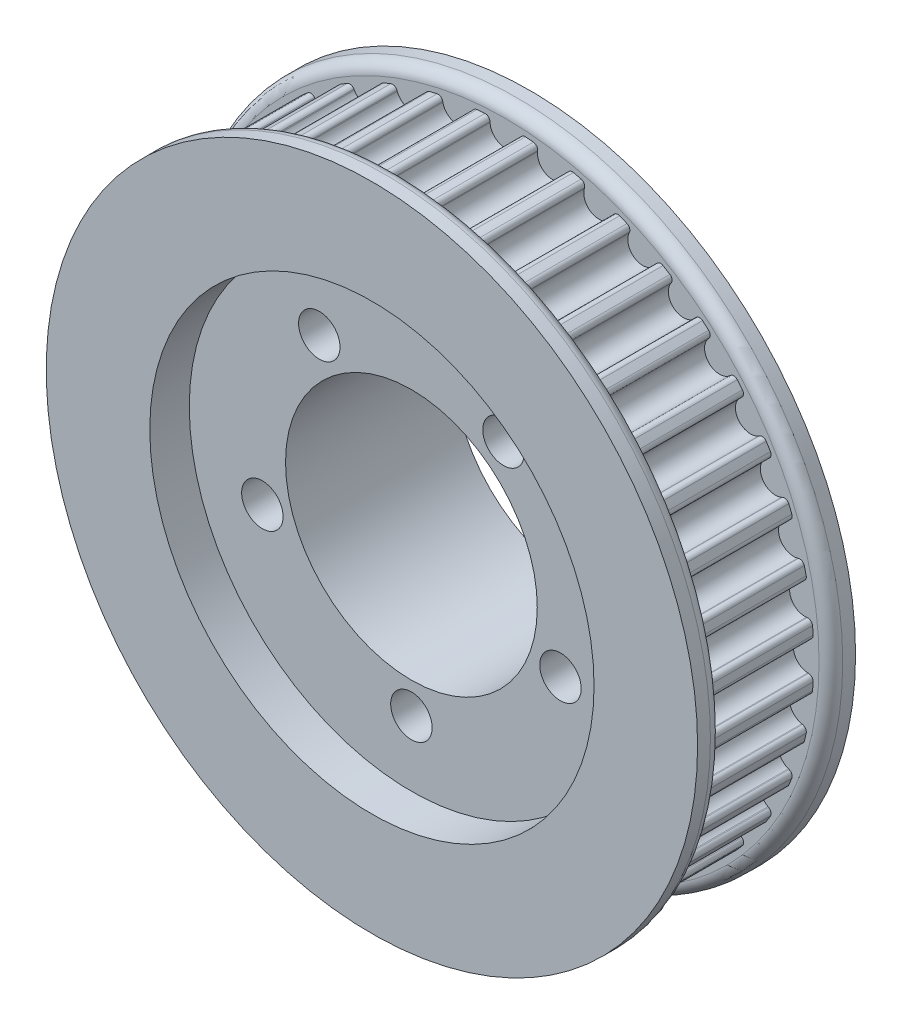
SolidWorks part; units mm, degrees
material "6061 합금"
ref_plane "정면" through (0, 0, 0) normal (0, 0, 1) x (1, 0, 0)
ref_plane "윗면" through (0, 0, 0) normal (0, 1, 0) x (1, 0, 0)
ref_plane "우측면" through (0, 0, 0) normal (1, 0, 0) x (0, 0, -1)
sketch "스케치3" plane through (0, 0, 0) normal (0, 0, 1) x (1, 0, 0)
  line L0 (0, 0) -> (0, 31.2595) construction
  line L1 (0, 0) -> (-4.9795, 31.4391) construction
  line L2 (0, 31.2595) -> (0, 32.9895) construction
  line L3 (-1.5331, 30.6478) -> (-1.5617, 31.2205)
  line L4 (1.5331, 30.6478) -> (1.5617, 31.2205)
  circle A0 centre (0, 0) radius 31.831 construction
  circle A1 centre (0, 0) radius 32.9895 construction
  circle A2 centre (0, 0) radius 31.2595
  circle A3 centre (0, 30.7245) radius 1.535
  dimension "D2" = 63.662
  dimension "D5" = 3.07
  dimension "D3" = 62.519
  dimension "D1" = 9
  dimension "D4" = 2.07
  dimension "D6" = 3.8
extrude "보스-돌출2" add sketch "스케치3" along normal mid plane 11 contours A2
extrude "컷-돌출2" cut sketch "스케치3<3>" against normal through all and the other way through all contours A3 A2 L3 | A2 A3 | A3 L4 A2 region at (0, 30.3451, 0) region at (-1.5216, 31.0799, 0) region at (1.5216, 31.0799, 0)
sketch "스케치3<3>" plane through (0, 0, 0) normal (0, 0, 1) x (1, 0, 0) same geometry as "스케치3"
fillet "필렛1" radius 0.48 2 edges at (1.5617, 31.2205, 0) (-1.5617, 31.2205, 0)
pattern_circular "원형 패턴1" count 40 over 360 about axis through (0, 0, 5.5) along (0, 0, -1) of "컷-돌출2", "필렛1"
sketch "스케치8" plane through (0, 0, 5.5) normal (0, 0, 1) x (1, 0, 0)
  circle A1 centre (0, 0) radius 32.9895 construction
  circle A2 centre (0, 0) radius 32.9895
extrude "보스-돌출3" add sketch "스케치8" along normal blind 2.5
fillet "필렛2" radius 1.2 1 edges at (32.9895, 0, 5.5)
mirror "대칭 복사1" about plane through (0, 0, 0) normal (0, 0, 1) of "보스-돌출3", "필렛2"
sketch "스케치17" plane through (0, 0, -8) normal (0, 0, -1) x (-1, 0, 0)
  circle A0 centre (0, 0) radius 20
  dimension "D1" = 40
extrude "보스-돌출4" add sketch "스케치17" along normal blind 5 contours A0
sketch "스케치10" plane through (0, 0, 0) normal (0, 0, 1) x (1, 0, 0)
  line L0 (0, 0) -> (0, 15.875) construction
  circle A0 centre (0, 15.875) radius 2.675
  circle A1 centre (9.3311, 12.8431) radius 2.675 construction
  circle A2 centre (15.098, 4.9056) radius 2.675
  circle A3 centre (15.098, -4.9056) radius 2.675 construction
  circle A4 centre (9.3311, -12.8431) radius 2.675
  circle A5 centre (0, -15.875) radius 2.675 construction
  circle A6 centre (-9.3311, -12.8431) radius 2.675
  circle A7 centre (-15.098, -4.9056) radius 2.675 construction
  circle A8 centre (-15.098, 4.9056) radius 2.675
  circle A9 centre (-9.3311, 12.8431) radius 2.675 construction
  point P25 (0, 0)
  dimension "D1" = 5.35
  dimension "D2" = 15.875
  dimension "D3" = 10
hole_wizard "M5x0.8 탭을 위한 탭 드릴2" positions "스케치14" profile "스케치15" hole size "M5x0.8" standard "Ansi Metric" end condition through all
sketch "스케치14" plane through (0, 0, 8) normal (0, 0, -1) x (-1, 0, 0)
  point P26 (-15.098, -4.9056)
  point P28 (0, -15.875)
  point P30 (15.098, -4.9056)
  point P32 (9.3311, 12.8431)
  point P34 (-9.3311, 12.8431)
sketch "스케치15" plane through (15.098, -4.9056, 8) normal (1, 0, 0) x (0, -1, 0)
  line L0 (0, 0) -> (0, 21)
  line L1 (0, 21) -> (2.1, 21)
  line L2 (2.1, 21) -> (2.1, 0)
  line L5 (2.1, 0) -> (0, 0)
  line L11 (0, -6.35) -> (0, 107.95) construction
  dimension "관통 구멍 지름" = 4.2
  dimension "관통 구멍 깊이" = 21
sketch "스케치16" plane through (0, 0, 8) normal (0, 0, 1) x (1, 0, 0)
  circle A0 centre (0, 0) radius 22.5
  dimension "D1" = 45
extrude "컷-돌출4" cut sketch "스케치16" against normal blind 4
sketch "스케치18" plane through (0, 0, 8) normal (0, 0, 1) x (1, 0, 0)
  circle A0 centre (0, 0) radius 12.75
  dimension "D1" = 25.5
extrude "컷-돌출5" cut sketch "스케치18" against normal through all
equation "\"n\"= 40'number of teeth"
equation "\"D2@스케치3\"=5*\"n\"/(PI)"
equation "\"D1@스케치3\"=360/\"n\""
equation "\"D1@원형 패턴1\"=\"n\""
equation "\"D3@스케치3\"=\"D2@스케치3\"-2*0.225*2.54"
